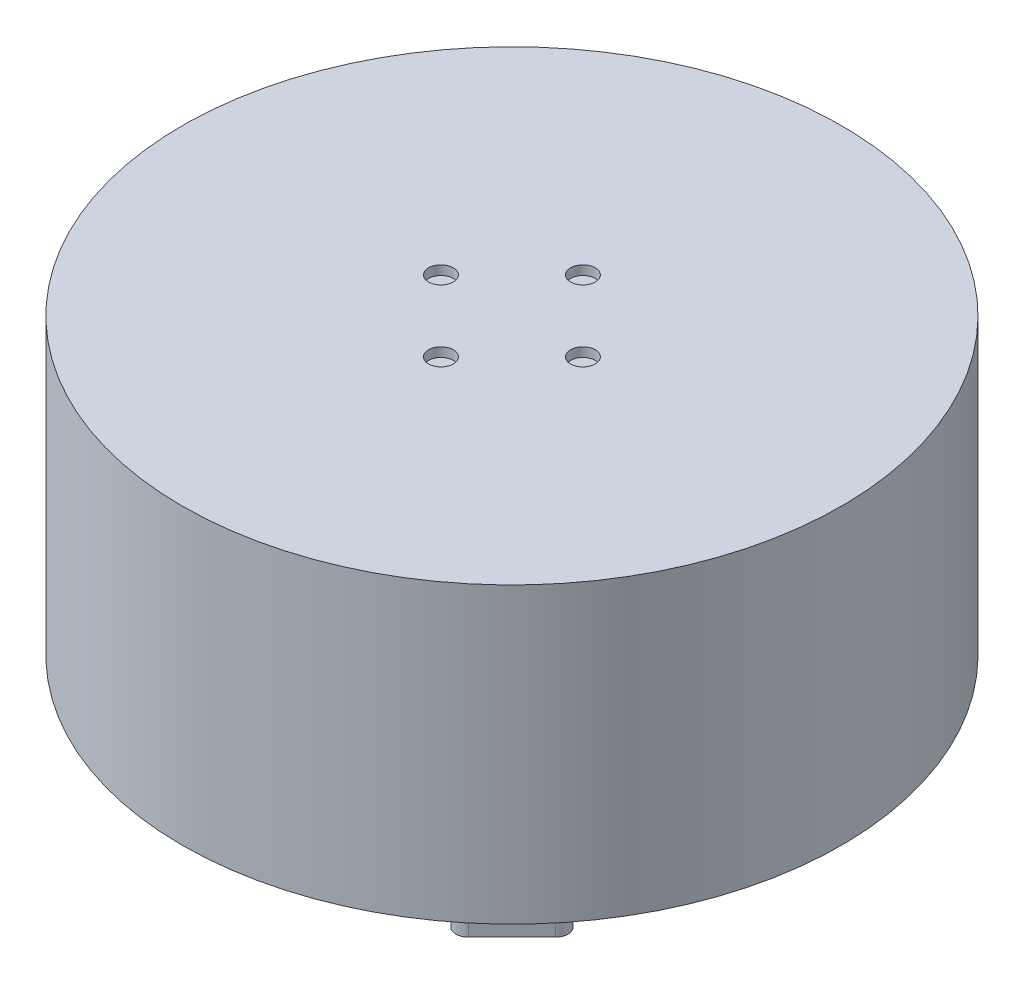
SolidWorks part; units mm, degrees
ref_plane "Front Plane" through (0, 0, 0) normal (0, 0, 1) x (1, 0, 0)
ref_plane "Top Plane" through (0, 0, 0) normal (0, 1, 0) x (1, 0, 0)
ref_plane "Right Plane" through (0, 0, 0) normal (1, 0, 0) x (0, 0, -1)
sketch "Sketch1" plane through (0, 0, 0) normal (0, 1, 0) x (1, 0, 0)
  circle A0 centre (0, 0) radius 53.4
  dimension "D1" = 106.8
extrude "Boss-Extrude1" add sketch "Sketch1" along normal blind 47.6
sketch "Sketch2" plane through (0, 0, 0) normal (0, -1, 0) x (1, 0, 0)
  circle A0 centre (0, 0) radius 20 construction
  circle A1 centre (0, 20) radius 2.5
  circle A2 centre (20, 0) radius 2.5
  circle A3 centre (0, -20) radius 2.5
  circle A4 centre (-20, 0) radius 2.5
  point P14 (0, 0)
  dimension "D1" = 40
  dimension "D2" = 5
  dimension "D3" = 4
extrude "Cut-Extrude1" cut sketch "Sketch2" against normal blind 1.5
sketch "Sketch3" plane through (0, 0, 0) normal (0, -1, 0) x (1, 0, 0)
  line L0 (0, 0) -> (0, 20) construction
  line L1 (0, 20) -> (20, 0) construction
  line L2 (20, 0) -> (0, 0) construction
  line L3 (0, 0) -> (32.1734, 32.1734) construction
  line L4 (28.6378, 35.7089) -> (35.7089, 28.6378) construction
  line L5 (30.7591, 37.8302) -> (37.8302, 30.7591) construction
  line L6 (26.5165, 33.5876) -> (33.5876, 26.5165) construction
  line L7 (30.052, 37.1231) -> (37.1231, 30.052)
  line L8 (27.2236, 34.2947) -> (34.2947, 27.2236)
  arc A0 (30.7591, 37.8302) -> (26.5165, 33.5876) centre (28.6378, 35.7089) ccw construction
  arc A1 (33.5876, 26.5165) -> (37.8302, 30.7591) centre (35.7089, 28.6378) ccw construction
  arc A2 (34.2947, 27.2236) -> (37.1231, 30.052) centre (35.7089, 28.6378) ccw
  arc A3 (30.052, 37.1231) -> (27.2236, 34.2947) centre (28.6378, 35.7089) ccw
  point P9 (32.1734, 32.1734)
  dimension "D3" = 3
  dimension "D1" = 45.5
  dimension "D2" = 10
  dimension "D4" = 1
extrude "Boss-Extrude2" add sketch "Sketch3" along normal blind 6
sketch "Sketch4" plane through (0, 47.6, 0) normal (0, 1, 0) x (1, 0, 0)
  circle A0 centre (0, 0) radius 11.5 construction
  circle A1 centre (0, 11.5) radius 2
  circle A2 centre (11.5, 0) radius 2
  circle A3 centre (0, -11.5) radius 2
  circle A4 centre (-11.5, 0) radius 2
  point P14 (0, 0)
  dimension "D3" = 4
  dimension "D1" = 23
  dimension "D2" = 4
extrude "Cut-Extrude2" cut sketch "Sketch4" against normal blind 1.5
equation "\"Np_b\" = 55"
equation "\"module\" = 0.5"
equation "\"pressure angle\" = 20.0"
equation "\"h_a\" = 0.5"
equation "\"h_b\" = 0.625"
equation "\"clr_tip_root\" = 0.125"
equation "\"fw_p_s\" = 15.81085678360617"
equation "\"Nr_s\" = 170"
equation "\"pressure_angle\" = 20.0"
equation "\"h_f\" = 0.625"
equation "\"dp_r_s\" = 85.0"
equation "\"db_r_s\" = 79.87387276680222"
equation "\"fw_r_s\" = 14.31085678360617"
equation "\"alpha_r_s\" = 0.8539582918412307"
equation "\"beta_r_s\" = 2.766740113094226"
equation "\"bearing_ID\" = 75"
equation "\"bearing_OD\" = 95"
equation "\"bearing_height\" = 10"
equation "\"clearance_planet\" = 1.5"
equation "\"case_dist\" = 6.5"
equation "\"Motor_case_OD_max\" = 131.3"
equation "\"case_mounting_PCD\" = 123.8"
equation "\"bearing mount thickness\" = 8"
equation "\"case_mounting_hole_dia\" = 3"
equation "\"output_mounting_PCD\" = 103"
equation "\"output_mounting_hole_dia\" = 4"
equation "\"clearance_case_mount_holes_shell_thickness\" = 1"
equation "\"motor_case_OD_base\" = 121.8"
equation "\"sec_carrier_thickness\" = 5"
equation "\"sun_coupler_hub_thickness\" = 4"
equation "\"clearance_sun_coupler_sec_carrier\" = 1.5"
equation "\"clearance_motor_and_case\" = 5"
equation "\"motor_OD\" = 106.8"
equation "\"Motor_case_thickness\" = 2.5"
equation "\"Motor_case_ID\" = 116.8"
equation "\"case_mounting_hole_shift\" = 1.0"
equation "\"output_mounting_nut_wrench_size\" = 7"
equation "\"output_mounting_nut_thickness\" = 3.2"
equation "\"case_mounting_hole_allen_socket_dia\" = 5.5"
equation "\"output_mounting_nut_depth\" = 3"
equation "\"case_mounting_bolt_depth\" = 4.5"
equation "\"Ns\" = 80"
equation "\"ring_radial_thickness\" = 5"
equation "\"ring_OD\"= \"Nr_s\" * \"module\" + \"ring_radial_thickness\" * 2"
equation "\"ring_to_chamfer_clearance\" = 1.5"
equation "\"Motor_case_OD_base_to_chamfer\" = 5"
equation "\"pattern_offset_from_motor_case_OD_base\" = 3"
equation "\"pattern_bulge_dia\" = 3"
equation "\"pattern_num_bulge\" = 18"
equation "\"pattern_depth\" = 2"
equation "\"motor_height\" = 47.6"
equation "\"case_mounting_wrench_size\" = 5.5"
equation "\"case_mounting_nut_clearance\" = 2"
equation "\"base_plate_thickness\" = 4"
equation "\"case_mounting_nut_thickness\" = 2.4"
equation "\"case_mounting_surface_height\" = 4"
equation "\"motor_mount_hole_PCD\" = 40"
equation "\"motor_mount_hole_dia\" = 5"
equation "\"motor_mount_hole_num\" = 4"
equation "\"central_hole_offset_from_motor_mount_PCD\" = 5"
equation "\"wire_slot_dist_from_center\" = 45.5"
equation "\"wire_slot_length\" = 10"
equation "\"wire_slot_radius\" = 3"
equation "\"driver_upper_holes_dist_from_center\" = 29"
equation "\"driver_lower_holes_dist_from_center\" = 13"
equation "\"driver_side_holes_dist_from_center\" = 22.5"
equation "\"driver_mount_holes_dia\" = 3"
equation "\"driver_mount_inserts_OD\" = 4.8"
equation "\"driver_mount_thickness\" = 1.5"
equation "\"driver_mount_height\" = 6"
equation "\"air_flow_hole_offset\" = 3"
equation "\"num_planet\" = 5"
equation "\"planet_pin_bolt_dia\" = 5"
equation "\"planet_pin_socket_head_dia\" = 8.5"
equation "\"carrier_PCD\" = 67.5"
equation "\"planet_shaft_dia\" = 8"
equation "\"planet_shaft_step_offset\" = 1"
equation "\"carrier_trapezoidal_support_sun_offset\" = 5"
equation "\"carrier_trapezoidal_support_hole_PCD_offset_bearing_ID\" = 4"
equation "\"carrier_trapezoidal_support_hole_dia\" = 3"
equation "\"carrier_trapezoidal_support_hole_socket_head_dia\" = 5.5"
equation "\"carrier_bearing_step_width\" = 1.5"
equation "\"standard_clearance_1_5mm\" = 1.5"
equation "\"standard_fillet_1_5mm\" = 1.5"
equation "\"sun_shaft_bearing_OD\" = 16"
equation "\"sun_shaft_bearing_width\" = 5"
equation "\"standard_bearing_insertion_chamfer\" = 0.5"
equation "\"carrier_trapezoidal_support_hole_wrench_size\" = 5.5"
equation "\"planet_pin_bolt_wrench_size\" = 8"
equation "\"planet_bearing_OD\" = 12"
equation "\"planet_bearing_width\" = 3.5"
equation "\"planet_bore\" = 10"
equation "\"D1@Boss-Extrude1\"=\"motor_height\""
equation "\"D1@Sketch1\"=\"motor_OD\""
equation "\"D1@Sketch2\"=\"motor_mount_hole_PCD\""
equation "\"D2@Sketch2\"=\"motor_mount_hole_dia\""
equation "\"D3@Sketch2\"=\"motor_mount_hole_num\""
equation "\"D1@Cut-Extrude1\"=\"standard_clearance_1_5mm\""
equation "\"D1@Sketch3\"=\"wire_slot_dist_from_center\""
equation "\"D2@Sketch3\"=\"wire_slot_length\""
equation "\"D3@Sketch3\"=\"wire_slot_radius\""
equation "\"D1@Boss-Extrude2\"=\"standard_clearance_1_5mm\"*4"
equation "\"motor_output_hole_PCD\" = 23"
equation "\"motor_output_hole_dia\" = 4"
equation "\"motor_output_hole_num\" = 4"
equation "\"D1@Sketch4\"=\"motor_output_hole_PCD\""
equation "\"D2@Sketch4\"=\"motor_output_hole_dia\""
equation "\"D3@Sketch4\"=\"motor_output_hole_num\""
equation "\"D1@Cut-Extrude2\"=\"standard_clearance_1_5mm\""
equation "\"dp_s\" = 40.0"
equation "\"db_s\" = 37.58770483143634"
equation "\"fw_s_calc\" = 4.872946430626146"
equation "\"alpha_s\" = 0.8539582918412272"
equation "\"beta_s\" = 0.5420834163175456"
equation "\"dp_p_b\" = 27.5"
equation "\"db_p_b\" = 25.84154707161248"
equation "\"alpha_p_b\" = 0.8539582918412449"
equation "\"beta_p_b\" = 1.564810689044783"
equation "\"sun_shaft_bearing_ID\" = 8"
equation "\"sun_hub_dia\" = 30.0"
equation "\"sun_central_bolt_dia\" = 5"
equation "\"sun_central_bolt_socket_head_dia\" = 8.5"
equation "\"fw_s_used\" = 44.67596466627659"
equation "\"motor_output_hole_CSK_OD\" = 8"
equation "\"motor_output_hole_CSK_head_height\" = 2.0"
equation "\"bearing_retainer_thickness\" = 2"
equation "\"Np_s\" = 35"
equation "\"fw_p_b\" = 21.365107882670422"
equation "\"dp_p_s\" = 17.5"
equation "\"db_p_s\" = 16.444620863753396"
equation "\"alpha_p_s\" = 0.8539582918412556"
equation "\"beta_p_s\" = 3.434940559174632"
equation "\"clr_tip_root_s\" = 0.125"
equation "\"Nr_b\" = 190"
equation "\"fw_r_b\" = 21.365107882670422"
equation "\"dp_r_b\" = 95.0"
equation "\"db_r_b\" = 89.2707989746613"
equation "\"alpha_r_b\" = 0.8539582918412414"
equation "\"beta_r_b\" = 2.655285004735114"
equation "\"ring_OD_b\" = 105.0"
equation "\"small_ring_case_thickness\" = 4"
equation "\"carrier_thickness\" = 4"
equation "\"small_ring_output_wall_thickness\" = 5"
equation "\"small_ring_output_wall_to_bearing_shaft_attachement_hole_dia\" = 4"
equation "\"small_ring_output_wall_to_bearing_shaft_attachement_hole_depth\" = 6.5"
equation "\"small_ring_output_wall_to_bearing_shaft_attachement_nut_wrench\" = 7"
equation "\"small_ring_output_wall_to_bearing_shaft_attachement_nut_thickness\" = 3.2"
equation "\"small_ring_output_wall_to_bearing_shaft_attachement_hole_pcd\" = 12"
equation "\"small_ring_output_wall_to_bearing_shaft_attachement_hole_num\" = 3"
equation "\"small_ring_output_wall_to_bearing_shaft_attachement_hole_CSK_OD\" = 8"
equation "\"small_ring_output_wall_to_bearing_shaft_attachement_hole_CSK_head_height\" = 2.0"
equation "\"carrier_small_ring_inner_bearing_ID\" = 20"
equation "\"carrier_small_ring_inner_bearing_OD\" = 32"
equation "\"carrier_small_ring_inner_bearing_height\" = 7"
equation "\"carrier_small_ring_inner_bearing_flap\" = 2"
equation "\"gear_casing_big_ring_to_bearing_dist\" = 24.81085678360617"
equation "\"gear_casing_thickness\" = 4"
